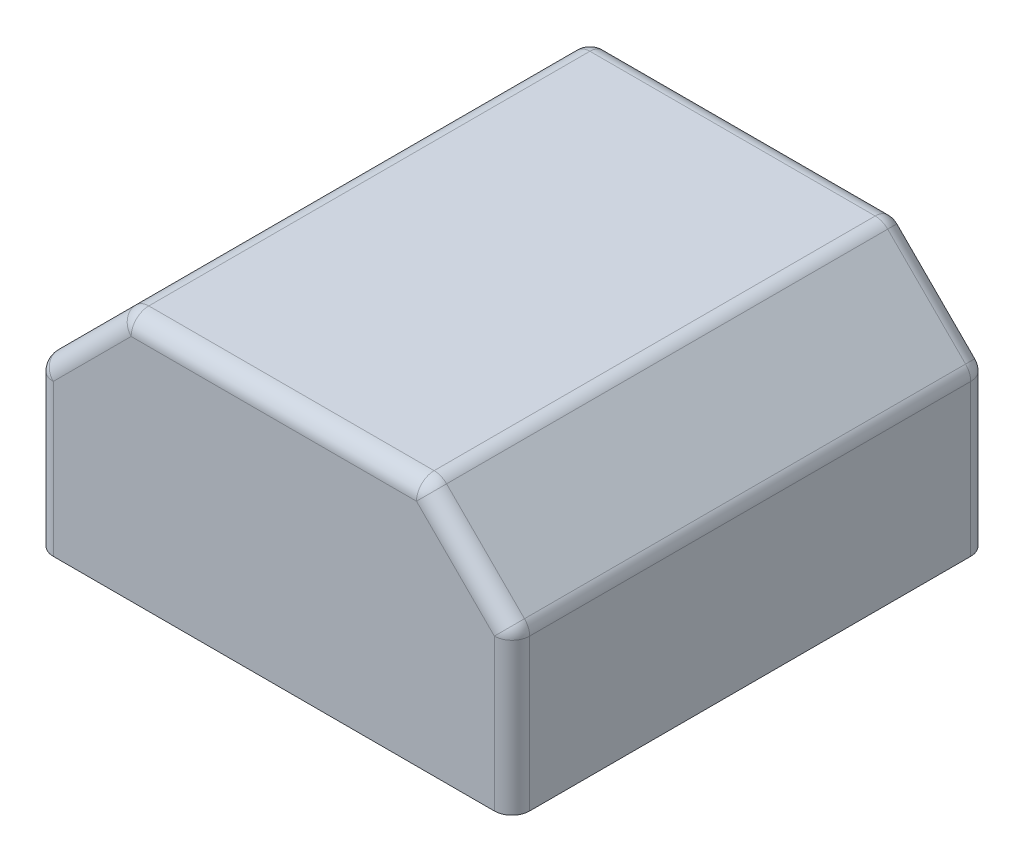
SolidWorks part; units mm, degrees
ref_plane "Front Plane" through (0, 0, 0) normal (0, 0, 1) x (1, 0, 0)
ref_plane "Top Plane" through (0, 0, 0) normal (0, 1, 0) x (1, 0, 0)
ref_plane "Right Plane" through (0, 0, 0) normal (1, 0, 0) x (0, 0, -1)
sketch "Sketch1" plane through (0, 0, 0) normal (0, 1, 0) x (1, 0, 0)
  line L1 (0, -5.7158) -> (4.95, -2.8579)
  line L2 (4.95, -2.8579) -> (4.95, 2.8579)
  line L3 (4.95, 2.8579) -> (0, 5.7158)
  line L4 (0, 5.7158) -> (-4.95, 2.8579)
  line L5 (-4.95, 2.8579) -> (-4.95, -2.8579)
  line L6 (-4.95, -2.8579) -> (0, -5.7158)
  line L7 (-6.75, 6.75) -> (6.75, 6.75)
  line L8 (-6.75, 6.75) -> (-6.75, -6.75)
  line L9 (-6.75, -6.75) -> (6.75, -6.75)
  line L10 (6.75, 6.75) -> (6.75, -6.75)
  line L11 (-6.75, 6.75) -> (6.75, -6.75) construction
  line L12 (-6.75, -6.75) -> (6.75, 6.75) construction
  circle A0 centre (0, 0) radius 4.95 construction
  dimension "D1" = 9.9
  dimension "D2" = 13.5
extrude "Boss-Extrude1" add sketch "Sketch1" along normal blind 5
sketch "Sketch3" plane through (0, 5, 0) normal (0, 1, 0) x (1, 0, 0)
  line L4 (6.75, 6.75) -> (-6.75, 6.75)
  line L5 (-6.75, 6.75) -> (-6.75, -6.75)
  line L6 (-6.75, -6.75) -> (6.75, -6.75)
  line L7 (6.75, -6.75) -> (6.75, 6.75)
  line L8 (6.75, 6.75) -> (-6.75, 6.75)
  line L9 (-6.75, 6.75) -> (-6.75, -6.75)
  line L10 (-6.75, -6.75) -> (6.75, -6.75)
  line L11 (6.75, -6.75) -> (6.75, 6.75)
  dimension "D1" = 0
extrude "Boss-Extrude2" add sketch "Sketch3" along normal blind 2
chamfer "Chamfer1" distance 2.5 angle 45 2 edges at (6.75, 7, 0) (-6.75, 7, 0)
fillet "Fillet2" radius 0.5 6 edges at (-4.95, 2.5, -2.8579) (-4.95, 2.5, 2.8579) (0, 2.5, 5.7158) (4.95, 2.5, 2.8579) (4.95, 2.5, -2.8579) (0, 2.5, -5.7158)
fillet "Fillet1" radius 0.5 14 edges at (-6.75, 2.25, -6.75) (-6.75, 2.25, 6.75) (6.75, 2.25, -6.75) (6.75, 2.25, 6.75) (-5.5, 5.75, -6.75) (0, 7, -6.75) (5.5, 5.75, -6.75) (5.5, 5.75, 6.75) (0, 7, 6.75) (-5.5, 5.75, 6.75) (6.75, 4.5, 0) (4.25, 7, 0) (-4.25, 7, 0) (-6.75, 4.5, 0)
